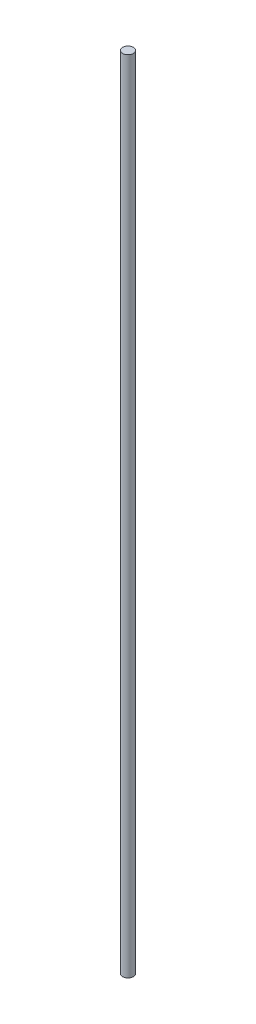
SolidWorks part; units mm, degrees
material "AISI 4340 Steel, normalized"
ref_plane "Front Plane" through (0, 0, 0) normal (0, 0, 1) x (1, 0, 0)
ref_plane "Top Plane" through (0, 0, 0) normal (0, 1, 0) x (1, 0, 0)
ref_plane "Right Plane" through (0, 0, 0) normal (1, 0, 0) x (0, 0, -1)
sketch "Sketch1" plane through (0, 0, 0) normal (0, 1, 0) x (1, 0, 0)
  circle A0 centre (0, 0) radius 2
  dimension "D1" = 4
extrude "Boss-Extrude1" add sketch "Sketch1" along normal blind 299
